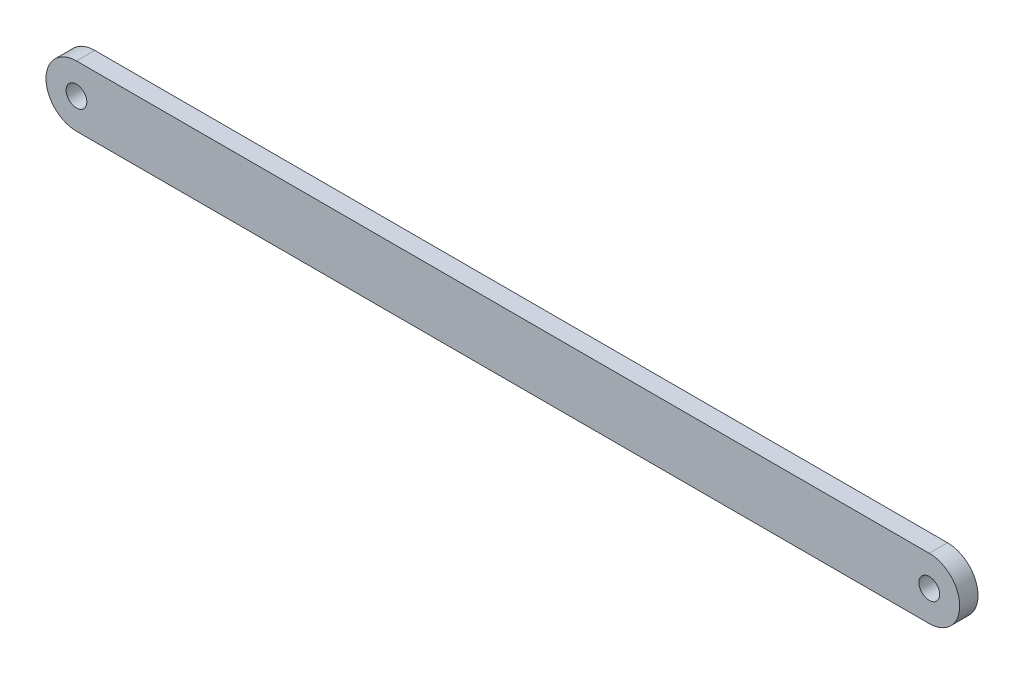
SolidWorks part; units mm, degrees
material "1023 Kohlenstoffstahlblech (SS)"
ref_plane "Ebene vorne" through (0, 0, 0) normal (0, 0, 1) x (1, 0, 0)
ref_plane "Ebene oben" through (0, 0, 0) normal (0, 1, 0) x (1, 0, 0)
ref_plane "Ebene rechts" through (0, 0, 0) normal (1, 0, 0) x (0, 0, -1)
sketch "Skizze1" plane through (0, 0, 0) normal (0, 0, 1) x (1, 0, 0)
  line L0 (-70, 0) -> (70, 0) construction
  line L1 (-70, 5) -> (70, 5)
  line L2 (-70, -5) -> (70, -5)
  arc A0 (-70, 5) -> (-70, -5) centre (-70, 0) ccw
  arc A1 (70, -5) -> (70, 5) centre (70, 0) ccw
  point P2 (0, 0)
  dimension "D1" = 140
  dimension "D2" = 10
extrude "Aufsatz-Linear austragen1" add sketch "Skizze1" along normal mid plane 3
hole_wizard "Durchgangsloch für M31" positions "Skizze2" profile "Skizze3" hole size "M3" standard "ANSI Metrisch" end condition through all
sketch "Skizze2" plane through (0, 0, 1.5) normal (0, 0, 1) x (1, 0, 0)
  arc A0 (-70, 5) -> (-70, -5) centre (-70, 0) ccw construction
  arc A1 (-70, 5) -> (-70, -5) centre (-70, 0) ccw construction
  arc A2 (70, -5) -> (70, 5) centre (70, 0) ccw construction
  arc A3 (70, -5) -> (70, 5) centre (70, 0) ccw construction
  point P1 (-70, 0)
  point P4 (70, 0)
sketch "Skizze3" plane through (-70, 0, 1.5) normal (1, 0, 0) x (0, -1, 0)
  line L0 (0, 0) -> (0, 3)
  line L1 (0, 3) -> (1.7, 3)
  line L2 (1.7, 3) -> (1.7, 0)
  line L5 (1.7, 0) -> (0, 0)
  line L11 (0, -6.35) -> (0, 107.95) construction
  dimension "Bohrerdurchmesser" = 3.4
  dimension "Bohrungstiefe" = 3
sketch "Skizze4" [suppressed] plane through (0, 0, 1) normal (0, 0, 1) x (1, 0, 0)
  line L0 (40, 5) -> (190, 5)
  line L1 (190, 5) -> (190, -5)
  line L2 (190, -5) -> (40, -5)
  arc A0 (40, -5) -> (40, 5) centre (40, 0) ccw construction
  arc A1 (40, -5) -> (40, 5) centre (40, 0) ccw
  dimension "D1" = 150
extrude "Aufsatz-Linear austragen2" [suppressed] add sketch "Skizze4" against normal up to surface (2 mm away) up to face at (-68.3, 0, -1.5)
